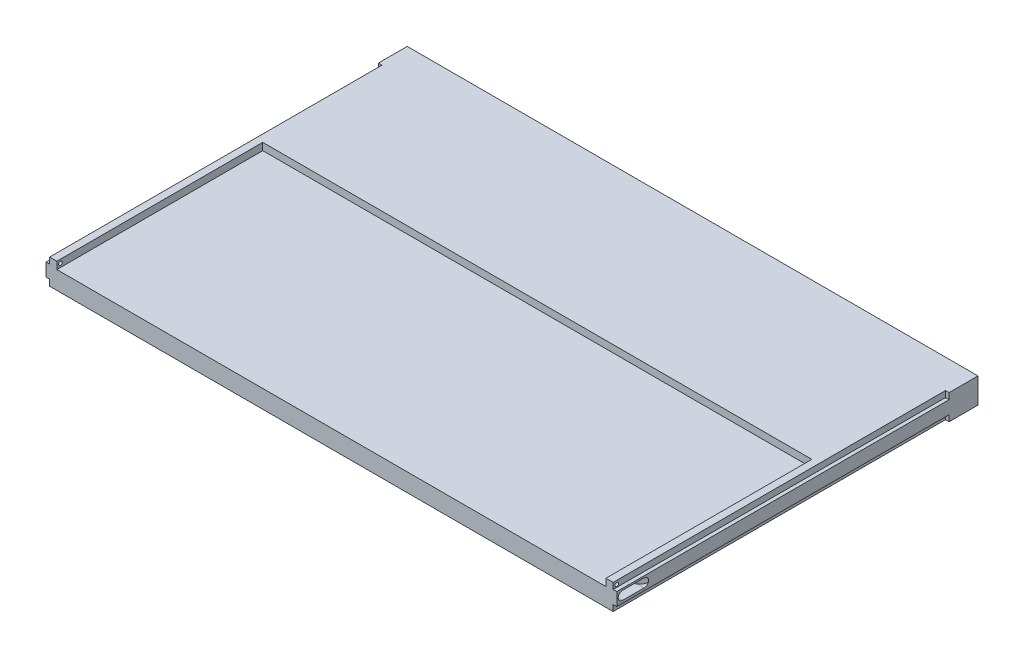
SolidWorks part; units mm, degrees
material "6061 Alloy"
ref_plane "Front Plane" through (0, 0, 0) normal (0, 0, 1) x (1, 0, 0)
ref_plane "Top Plane" through (0, 0, 0) normal (0, 1, 0) x (1, 0, 0)
ref_plane "Right Plane" through (0, 0, 0) normal (1, 0, 0) x (0, 0, -1)
sketch "Sketch1" plane through (0, 0, 0) normal (0, 1, 0) x (1, 0, 0)
  line L1 (-247.65, 158.75) -> (247.65, 158.75)
  line L2 (-247.65, 158.75) -> (-247.65, -158.75)
  line L3 (-247.65, -158.75) -> (247.65, -158.75)
  line L4 (247.65, 158.75) -> (247.65, -158.75)
  line L5 (-247.65, 158.75) -> (247.65, -158.75) construction
  line L6 (-247.65, -158.75) -> (247.65, 158.75) construction
  point P0 (0, 0)
  dimension "D1" = 495.3
  dimension "D2" = 317.5
extrude "Boss-Extrude1" add sketch "Sketch1" along normal blind 15.875
sketch "Sketch2" plane through (0, 15.875, 0) normal (0, 1, 0) x (1, 0, 0)
  line L0 (-247.65, -158.75) -> (247.65, -158.75) construction
  line L1 (-247.65, 158.75) -> (-241.3, 158.75)
  line L2 (-247.65, 158.75) -> (-247.65, -158.75)
  line L3 (-247.65, -158.75) -> (-241.3, -158.75)
  line L4 (-241.3, 22.225) -> (-241.3, -158.75)
  line L5 (247.65, 158.75) -> (-247.65, 158.75) construction
  line L6 (247.65, 158.75) -> (241.3, 158.75)
  line L7 (247.65, 158.75) -> (247.65, -158.75)
  line L8 (247.65, -158.75) -> (241.3, -158.75)
  line L9 (241.3, 22.225) -> (241.3, -158.75)
  line L10 (-241.3, 158.75) -> (241.3, 158.75)
  line L12 (-241.3, 22.225) -> (241.3, 22.225)
  point P14 (-244.475, -158.75)
  dimension "D1" = 6.35
  dimension "D2" = 180.975
extrude "Boss-Extrude2" add sketch "Sketch2" along normal blind 6.35
sketch "Sketch3" plane through (-247.65, 0, 0) normal (-1, 0, 0) x (0, 0, 1)
  line L0 (158.75, 22.225) -> (158.75, 0) construction
  line L1 (-158.75, 22.225) -> (158.75, 22.225) construction
  circle A0 centre (155.575, 19.05) radius 1.5875
  dimension "D3" = 3.175
  dimension "D1" = 3.175
  dimension "D2" = 3.175
extrude "Cut-Extrude1" cut sketch "Sketch3" against normal through all
sketch "Sketch4" plane through (0, 0, 158.75) normal (0, 0, 1) x (1, 0, 0)
  line L0 (-247.65, 22.225) -> (-247.65, 0) construction
  line L1 (-247.65, 16.8275) -> (-250.825, 16.8275)
  line L2 (-247.65, 16.8275) -> (-247.65, 5.3975)
  line L3 (-247.65, 5.3975) -> (-250.825, 5.3975)
  line L4 (-250.825, 16.8275) -> (-250.825, 5.3975)
  point P12 (-247.65, 11.1125)
  dimension "D1" = 11.43
  dimension "D2" = 3.175
extrude "Boss-Extrude3" add sketch "Sketch4" against normal blind 292.1
sketch "Sketch5" plane through (-247.65, 0, 0) normal (-1, 0, 0) x (0, 0, 1)
  line L0 (-158.75, 0) -> (158.75, 0) construction
  line L1 (-158.75, 22.225) -> (-133.35, 22.225)
  line L2 (-158.75, 22.225) -> (-158.75, 0)
  line L3 (-158.75, 0) -> (-133.35, 0)
  line L4 (-133.35, 22.225) -> (-133.35, 0)
  line L5 (-133.35, 5.3975) -> (-133.35, 16.8275) construction
extrude "Boss-Extrude4" add sketch "Sketch5" along normal up to surface (3.175 mm away) up to face at (-250.825, 11.1125, 12.7)
mirror "Mirror1" about plane through (0, 0, 0) normal (1, 0, 0) of "Boss-Extrude4", "Boss-Extrude3"
sketch "Sketch6" plane through (-247.65, 0, 0) normal (-1, 0, 0) x (0, 0, 1)
  line L0 (153.67, 11.43) -> (134.62, 11.43) construction
  line L1 (153.67, 7.62) -> (134.62, 7.62)
  line L2 (153.67, 15.24) -> (134.62, 15.24)
  line L3 (158.75, 5.3975) -> (158.75, 0) construction
  line L4 (-133.35, 0) -> (158.75, 0) construction
  arc A0 (153.67, 7.62) -> (153.67, 15.24) centre (153.67, 11.43) ccw
  arc A1 (134.62, 15.24) -> (134.62, 7.62) centre (134.62, 11.43) ccw
  point P2 (144.145, 11.43)
  dimension "D1" = 19.05
  dimension "D2" = 5.08
  dimension "D3" = 7.62
  dimension "D4" = 11.43
extrude "Cut-Extrude2" cut sketch "Sketch6" against normal blind 25.4 from surface starting at face at (-250.825, 11.1125, -66.675)
extrude "Cut-Extrude3" cut sketch "Sketch6<2>" along normal blind 25.4 from surface starting at face at (250.825, 11.1125, -66.675)
sketch "Sketch6<2>" plane through (-247.65, 0, 0) normal (-1, 0, 0) x (0, 0, 1) same geometry as "Sketch6"
sketch "Sketch11" plane through (0, 0, 0) normal (0, -1, 0) x (1, 0, 0)
  line L0 (-250.825, 130.81) -> (-225.425, 130.81)
  line L1 (-225.425, 130.81) -> (-225.425, 147.32)
  line L2 (-225.425, 147.32) -> (-250.825, 130.81)
  line L3 (-225.425, 134.62) -> (-225.425, 153.67) construction
  dimension "D1" = 10.16
extrude "Boss-Extrude5" add sketch "Sketch11" against normal up to surface (15.24 mm away) from surface up to face at (-238.125, 15.24, 144.145) starting at face at (-238.125, 7.62, 144.145)
mirror "Mirror2" about plane through (0, 0, 0) normal (1, 0, 0) of "Boss-Extrude5"
